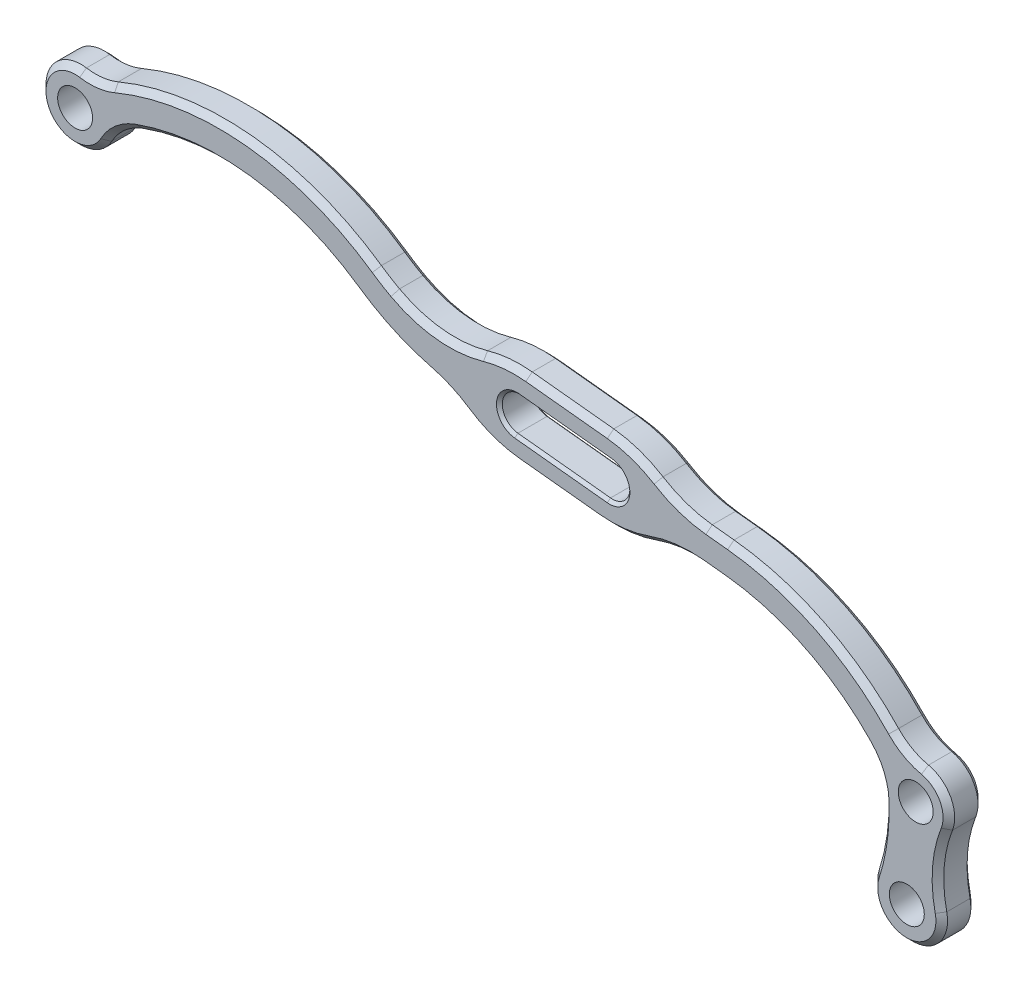
SolidWorks part; units mm, degrees
note: The reader was unsure of these and kept them because the rebuilt part matched: shared geometry of "Sketch4<2>".
ref_plane "Спереди" through (0, 0, 0) normal (0, 0, 1) x (1, 0, 0)
ref_plane "Сверху" through (0, 0, 0) normal (0, 1, 0) x (1, 0, 0)
ref_plane "Справа" through (0, 0, 0) normal (1, 0, 0) x (0, 0, -1)
other "Configuration Table"
sketch "Sketch1" plane through (0, 0, 5) normal (0, 0, 1) x (1, 0, 0)
  line L0 (72.4787, 6.0336) -> (94.9418, 3.6726)
  line L1 (80.4883, 8.2083) -> (89.9363, 7.2152) construction
  line L2 (36.385, 6.5) -> (39, 6.5)
  line L3 (35.2523, 11.1565) -> (36.385, 6.5)
  line L4 (80.4883, 8.2083) -> (89.9363, 7.2152) construction
  arc A0 (40.881, 10.4938) -> (63.9587, 9.1988) centre (51.3653, -8.9473) cw
  circle A1 centre (111.1997, -6.0169) radius 2.85
  arc A2 (39, 6.5) -> (37.6854, 12.1966) centre (39, 9.5) ccw
  arc A3 (35.2523, 11.1565) -> (37.6854, 12.1966) centre (26, 36.1667) ccw
  arc A4 (39, 6.5) -> (37.6854, 12.1966) centre (39, 9.5) ccw construction
  circle A6 centre (111.1997, -6.0169) radius 2.85
  circle A7 centre (110.4359, -14.0152) radius 1.5 construction
  circle A8 centre (110.4359, -14.0152) radius 3
  circle A9 centre (110.4359, -14.0152) radius 1.5
  circle A10 centre (111.1997, -6.0169) radius 1.5
  arc A11 (108.36, -6.2592) -> (107.5809, -13.0939) centre (90.9923, -7.7411) cw
  arc A12 (113.8545, -7.0535) -> (113.3652, -13.3677) centre (124.0032, -11.016) ccw
  circle A13 centre (39, 9.5) radius 3
  circle A14 centre (39, 9.5) radius 1.5
  arc A15 (63.9587, 9.1988) -> (72.4787, 6.0336) centre (74.3914, 24.2316) ccw
  arc A17 (94.9418, 3.6726) -> (109.7835, -4.7641) centre (92.7146, -17.5185) cw
  circle A18 centre (84.8987, 4.7282) radius 1.5 construction
  circle A19 centre (84.8987, 4.7282) radius 1.5
  arc A22 (64.2892, 10.447) -> (76.3424, 5.2756) centre (78.6577, 27.304) ccw construction
  dimension "D3" = 6
  dimension "D4" = 3
  dimension "D5" = 6
  dimension "D6" = 3
  dimension "D1" = 0
  dimension "D2" = 0
extrude "Boss-Extrude1" add sketch "Sketch1" along normal blind 3
sketch "Sketch3" plane through (0, 0, 5) normal (0, 0, 1) x (1, 0, 0)
  line L0 (72.4787, 6.0336) -> (94.9418, 3.6726) construction
  line L1 (72.4787, 6.0336) -> (94.9418, 3.6726)
  arc A0 (109.7835, -4.7641) -> (94.9418, 3.6726) centre (92.7146, -17.5185) ccw construction
  arc A1 (63.9587, 9.1988) -> (72.4787, 6.0336) centre (74.3914, 24.2316) ccw construction
  arc A2 (63.9587, 9.1988) -> (40.881, 10.4938) centre (51.3653, -8.9473) ccw construction
  arc A3 (109.7835, -4.7641) -> (94.9418, 3.6726) centre (92.7146, -17.5185) ccw
  arc A4 (63.9587, 9.1988) -> (72.4787, 6.0336) centre (74.3914, 24.2316) ccw
  arc A5 (63.9587, 9.1988) -> (40.881, 10.4938) centre (51.3653, -8.9473) ccw
extrude "Extrude-Thin1" add sketch "Sketch3" along normal blind 3 thin thin type mid plane wall 3
sketch "Sketch4" plane through (0, 0, 8) normal (0, 0, 1) x (1, 0, 0)
  line L0 (71.8385, 9.6201) -> (90.7344, 7.6341)
  line L1 (71.8385, 9.6201) -> (71.1068, 2.6585)
  line L2 (90.7344, 7.6341) -> (90.0027, 0.6724)
  line L3 (71.1068, 2.6585) -> (90.0027, 0.6724)
  line L4 (95.0986, 5.1644) -> (72.6355, 7.5254) construction
  line L5 (95.0986, 5.1644) -> (72.6355, 7.5254) construction
  line L7 (94.785, 2.1808) -> (72.3219, 4.5418) construction
  line L8 (76.9425, 5.5644) -> (84.8987, 4.7282) construction
  line L9 (77.0993, 7.0562) -> (85.0555, 6.22)
  line L10 (76.7857, 4.0726) -> (84.7419, 3.2364)
  circle A36 centre (84.8987, 4.7282) radius 1.5
  circle A37 centre (84.8987, 4.7282) radius 1.5 construction
  arc A38 (77.0993, 7.0562) -> (76.7857, 4.0726) centre (76.9425, 5.5644) ccw
  arc A39 (84.7419, 3.2364) -> (85.0555, 6.22) centre (84.8987, 4.7282) ccw
  point P5 (80.9206, 5.1463)
  dimension "D1" = 2
  dimension "D4" = 1.5
  dimension "D7" = 4
  dimension "D2" = 2
  dimension "D5" = 8
  dimension "D6" = 4
  dimension "D3" = 0
extrude "Boss-Extrude2" add sketch "Sketch4" against normal up to surface (3 mm away) up to face at (86.0676, 0.9668, 5)
fillet "Fillet1" radius 10 4 edges at (90.0027, 0.6724, 6.5) (90.7344, 7.6341, 6.5) (71.1068, 2.6585, 6.5) (71.8385, 9.6201, 6.5)
fillet "Fillet2" radius 10 4 edges at (90.2118, 2.6615, 6.5) (71.3186, 4.6732, 6.5) (71.6326, 7.6614, 6.5) (90.5254, 5.6451, 6.5)
fillet "Fillet3" radius 5 4 edges at (108.4097, -5.435, 6.5) (110.5094, -3.2518, 6.5) (41.9978, 9.3861, 6.5) (40.5973, 12.0394, 6.5)
extrude "Cut-Extrude2" cut sketch "Sketch4<2>" against normal blind 3 contours A38 L10 A39 L9
sketch "Sketch4<2>" plane through (0, 0, 8) normal (0, 0, 1) x (1, 0, 0) same geometry as "Sketch4"
chamfer "Chamfer1" distance 0.25 angle 45 8 edges at (86.3905, 4.5714, 8) (86.3905, 4.5714, 5) (81.0774, 6.6381, 8) (81.0774, 6.6381, 5) (80.7638, 3.6545, 8) (80.7638, 3.6545, 5) (75.4508, 5.7212, 8) (75.4508, 5.7212, 5)
fillet "Fillet4" radius 0.5 54 edges at (80.5718, 1.6637, 5) (80.5718, 1.6637, 8) (81.2661, 8.6293, 8) (75.8318, 9.0125, 8) (86.2859, 1.3177, 8) (81.2661, 8.6293, 5) (74.7466, 2.5711, 5) (86.9646, 7.7757, 5) (74.7466, 2.5711, 8) (66.1672, 6.2223, 8) (66.1672, 6.2223, 5) (65.5775, 9.9313, 8) (65.5775, 9.9313, 5) (75.8318, 9.0125, 5) (86.2859, 1.3177, 5) (53.8144, 14.5131, 5) (86.9646, 7.7757, 8) (71.0975, 4.4899, 5) (54.0154, 11.4693, 8) (71.0975, 4.4899, 8) (70.0687, 8.3171, 5) (70.0687, 8.3171, 8) (90.6644, 2.3593, 8) (90.6644, 2.3593, 5) (91.0309, 5.8465, 8) (91.0309, 5.8465, 5) (93.8499, 2.2791, 8) (101.4396, 0.2642, 5) (101.4396, 0.2642, 8) (108.2583, -10.1322, 5) (108.2583, -10.1322, 8) (102.7851, 2.9457, 5) (102.7851, 2.9457, 8) (36.3099, 8.172, 5) (36.3099, 8.172, 8) (94.1635, 5.2627, 5) (108.0198, -5.3349, 8) (108.0198, -5.3349, 5) (110.4079, -2.7042, 8) (110.4079, -2.7042, 5) (42.7734, 9.4873, 8) (42.7734, 9.4873, 5) (40.8653, 12.4347, 8) (94.1635, 5.2627, 8) (40.8653, 12.4347, 5) (53.8144, 14.5131, 8) (54.0154, 11.4693, 5) (93.8499, 2.2791, 5) (113.7101, -4.6677, 5) (110.2941, -17.0118, 8) (113.7101, -4.6677, 8) (113.1409, -10.1742, 5) (110.2941, -17.0118, 5) (113.1409, -10.1742, 8) profile chamfer
